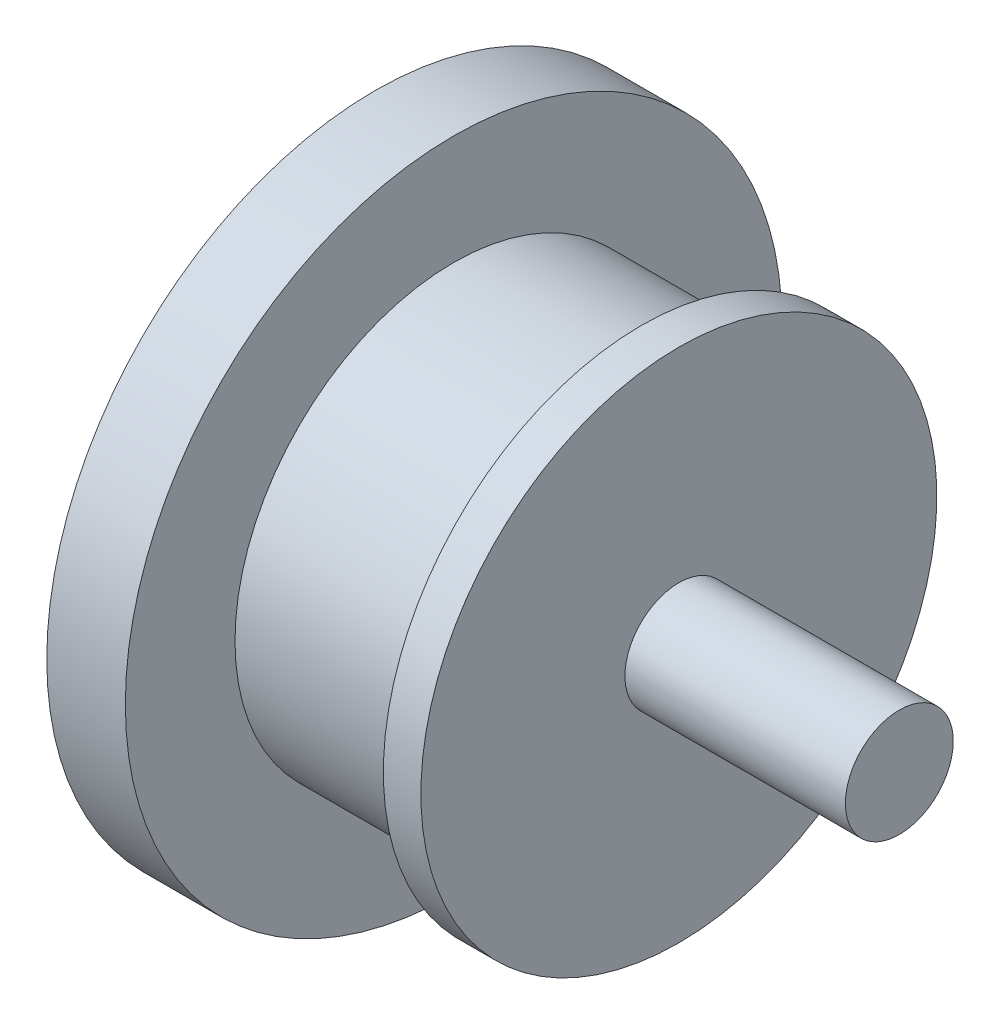
SolidWorks part; units mm, degrees
material "6061-T6 (SS)"
ref_plane "Front Plane" through (0, 0, 0) normal (0, 0, 1) x (1, 0, 0)
ref_plane "Top Plane" through (0, 0, 0) normal (0, 1, 0) x (1, 0, 0)
ref_plane "Right Plane" through (0, 0, 0) normal (1, 0, 0) x (0, 0, -1)
sketch "Sketch1" plane through (0, 0, 0) normal (0, 0, 1) x (1, 0, 0)
  line L0 (-7.35, 14) -> (-4, 14)
  line L1 (5.6, 0) -> (15, 0)
  line L2 (-4, 14) -> (-4, 9.325)
  line L3 (-4, 9.325) -> (4, 9.325)
  line L4 (4, 9.325) -> (4, 11)
  line L5 (4, 11) -> (5.6, 11)
  line L6 (5.6, 11) -> (5.6, 2.3)
  line L7 (5.6, 0) -> (-7.35, 0)
  line L8 (0, 0) -> (-7.35, 0) construction
  line L9 (15, 0) -> (15, 2.3)
  line L10 (-7.55, 14) -> (-9.65, 14)
  line L11 (0, 9.325) -> (0, 0) construction
  line L12 (-9.65, -14) -> (-7.55, -14)
  line L13 (15, 2.3) -> (5.6, 2.3)
  line L14 (-7.55, 14) -> (-9.65, 14) construction
  line L17 (-7.35, 13.8) -> (-7.35, 5)
  line L18 (-7.35, -5) -> (-7.35, -13.8)
  line L20 (-7.35, 0) -> (-7.35, 14)
  line L22 (-7.35, 13.8) -> (-7.35, 5) construction
  dimension "D1" = 15
  dimension "D2" = 1.675
  dimension "D3" = 18.65
  dimension "D4" = 8
  dimension "D5" = 2.3
  dimension "D6" = 1.6
revolve "Revolve1" add sketch "Sketch1" angle 360 about L8
ref_axis "Axis1" through (-5.6, 0, 0) along (1, 0, 0)
